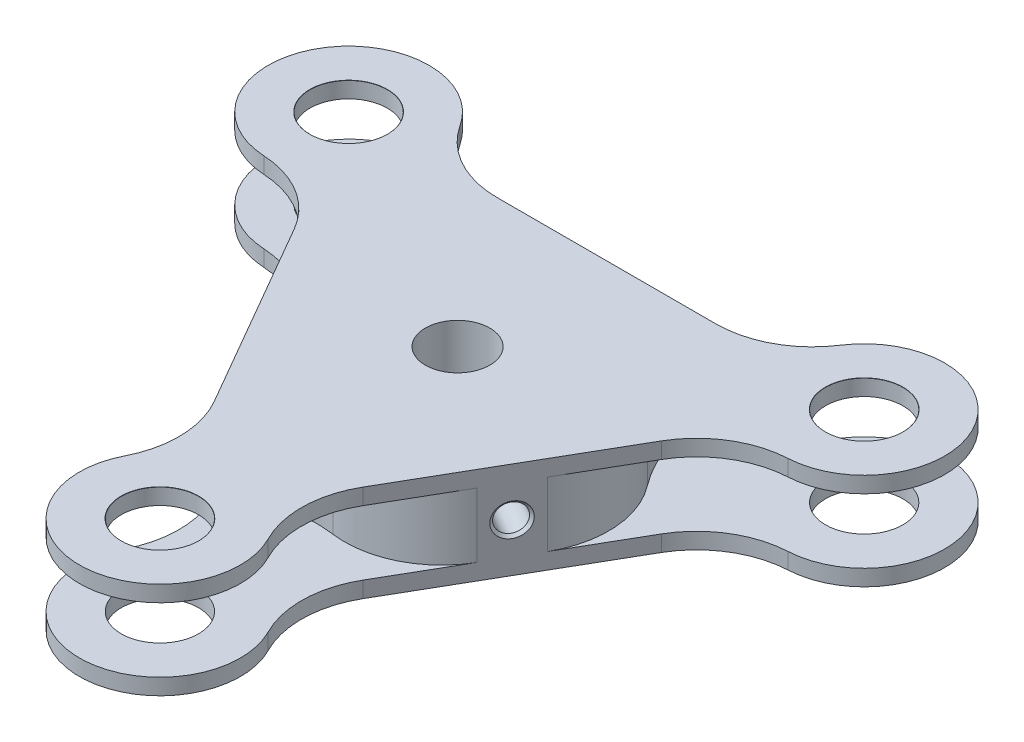
SolidWorks part; units mm, degrees
ref_plane "Plan de face" through (0, 0, 0) normal (0, 0, 1) x (1, 0, 0)
ref_plane "Plan de dessus" through (0, 0, 0) normal (0, 1, 0) x (1, 0, 0)
ref_plane "Plan de droite" through (0, 0, 0) normal (1, 0, 0) x (0, 0, -1)
sketch "Esquisse1" plane through (0, 0, 0) normal (0, 1, 0) x (1, 0, 0)
  line L3 (20, -11.547) -> (-40, 23.094) construction
  line L6 (-20, -11.547) -> (40, 23.094) construction
  line L16 (40, 23.094) -> (0, -46.188)
  line L17 (0, -46.188) -> (-40, 23.094)
  line L19 (-40, 23.094) -> (40, 23.094)
  circle A6 centre (0, 0) radius 5
  circle A7 centre (40, 23.094) radius 12.5
  circle A9 centre (0, -46.188) radius 12.5
  circle A10 centre (-40, 23.094) radius 12.5
  point P11 (0, 0)
  point P12 (5.3523, 54.348)
  point P36 (0, 50)
  point P38 (0, 50)
  point P40 (0, 50)
  point P41 (0, 50)
  dimension "D2" = 5.3523
  dimension "D3" = 80
  dimension "D5" = 25
  dimension "D1" = 80
  dimension "D6" = 25
  dimension "D8" = 10
  dimension "D7" = 25
  dimension "D4" = 80
extrude "Boss.-Extru.1" add sketch "Esquisse1" along normal mid plane 15 contours A10 L17 A9 L16 A7 L19 A6 | L19 A10 L17 | L16 A7 L19 | L19 A7 L16 | L17 A10 L19 | L17 A9 L16 | L16 A9 L17 region at (41.3783, 0, -23.8898) region at (33.1084, 0, -19.1151) region at (19.2267, 0, 11.1005) region at (0, 0, 47.7796) region at (0, 0, 38.2303) region at (-33.1084, 0, -19.1151) region at (-41.3783, 0, -23.8898)
sketch "Esquisse7" plane through (0, 0, 0) normal (0, 1, 0) x (1, 0, 0)
  circle A9 centre (-40, 23.094) radius 24
  circle A10 centre (0, -46.188) radius 24
  circle A11 centre (40, 23.094) radius 24
  dimension "D1" = 48
  dimension "D2" = 48
  dimension "D3" = 48
extrude "Enlèv. mat.-Extru.1" cut sketch "Esquisse7" against normal mid plane 10
sketch "Esquisse14" plane through (0, 7.5, 0) normal (0, 1, 0) x (1, 0, 0)
  arc A0 (-27.5, 23.094) -> (-33.75, 12.2687) centre (-40, 23.094) ccw construction
  arc A2 (-6.25, -35.3627) -> (6.25, -35.3627) centre (0, -46.188) ccw construction
  arc A3 (33.75, 12.2687) -> (27.5, 23.094) centre (40, 23.094) ccw construction
  point P17 (-40, 23.094)
  point P21 (40, 23.094)
  point P24 (0, -46.188)
sketch "Esquisse18" plane through (0, 7.5, 0) normal (0, 1, 0) x (1, 0, 0)
  point P0 (-40, 23.094)
  point P3 (40, 23.094)
  point P6 (0, -46.188)
hole_wizard "Dégagement M102" positions "Esquisse18" profile "Esquisse17" hole size "M10" standard "ISO" end condition through all
sketch "Esquisse17" plane through (-40, 7.5, -23.094) normal (1, 0, 0) x (0, 0, 1)
  line L0 (0, 0) -> (0, 15)
  line L1 (0, 15) -> (6, 15)
  line L2 (6, 15) -> (6, 0.025)
  line L3 (6, 0.025) -> (6.025, 0)
  line L5 (6.025, 0) -> (0, 0)
  line L6 (-6, 0.025) -> (-6.025, 0) construction
  line L11 (0, -6.35) -> (0, 107.95) construction
  dimension "Diamètre du perçage jusqu'au prochain" = 12
  dimension "Profondeur du perçage jusqu'au prochain" = 15
  dimension "Diamètre du fraisage entrant" = 12.05
  dimension "Angle du fraisage entrant" = 90
sketch "Esquisse21" plane through (0, 0, -23.094) normal (0, 0, -1) x (-1, 0, 0)
  line L1 (-25, -5) -> (25, -5)
  line L2 (-25, -5) -> (-25, 5)
  line L3 (-25, 5) -> (25, 5)
  line L4 (25, -5) -> (25, 5)
  line L5 (-25, -5) -> (25, 5) construction
  line L6 (-25, 5) -> (25, -5) construction
  point P0 (0, 0)
  dimension "D1" = 10
  dimension "D2" = 50
fillet "Congé6" radius 15 6 edges at (28, 0, -2.3094) (12, 0, 25.4034) (-28, 0, -2.3094) (-12, 0, 25.4034) (16, 0, -23.094) (-16, 0, -23.094)
sketch "Esquisse22" plane through (20, 0, 11.547) normal (0.866, 0, 0.5) x (0.5, 0, -0.866)
  point P0 (0, 0)
  point P3 (0, 0)
hole_wizard "Trou taraudé M51" positions "Esquisse22" profile "Esquisse23" tap size "M5" standard "ISO" end condition up to next
sketch "Esquisse23" plane through (20, 0, 11.547) normal (0, 1, 0) x (0.5, 0, -0.866)
  line L0 (0, 0) -> (0, 45.282)
  line L1 (0, 45.282) -> (2.1, 45.282)
  line L2 (2.1, 45.282) -> (2.1, 0.425)
  line L3 (2.1, 0.425) -> (2.525, 0)
  line L5 (2.525, 0) -> (0, 0)
  line L6 (-2.1, 0.425) -> (-2.525, 0) construction
  line L11 (0, -6.35) -> (0, 107.95) construction
  dimension "Diamètre du trou pour taraudage jusqu'au prochain" = 4.2
  dimension "Profondeur du trou pour taraudage jusqu'au prochain" = 45.282
  dimension "Diamètre du fraisage entrant" = 5.05
  dimension "Angle du fraisage entrant" = 90
cosmetic thread "Filetage de perçage2" parameters "D2"=5
cosmetic thread "Filetage de perçage3" parameters "D2"=5.85
fillet "Congé7" radius 15 12 edges at (27.5, 6.25, -23.094) (27.5, -6.25, -23.094) (-27.5, -6.25, -23.094) (-27.5, 6.25, -23.094) (-33.75, 6.25, -12.2687) (-33.75, -6.25, -12.2687) (-6.25, -6.25, 35.3627) (-6.25, 6.25, 35.3627) (6.25, -6.25, 35.3627) (6.25, 6.25, 35.3627) (33.75, 6.25, -12.2687) (33.75, -6.25, -12.2687)
